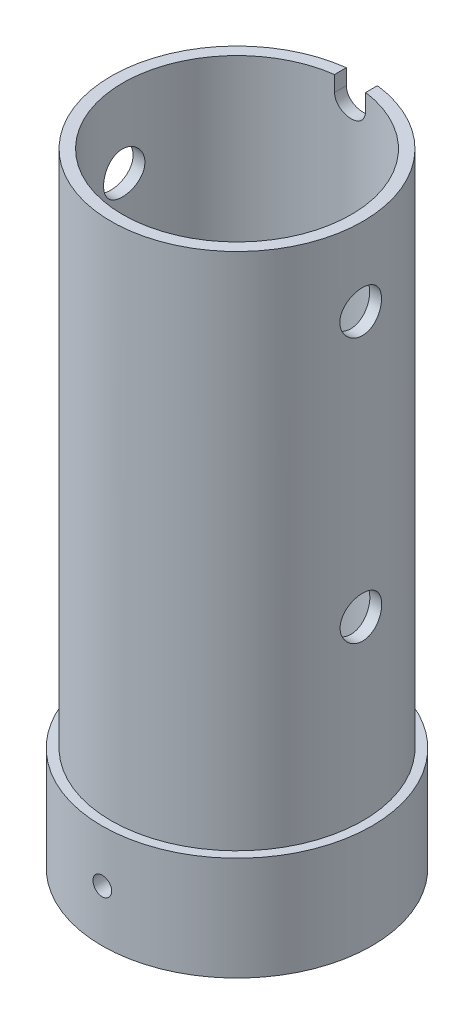
SolidWorks part; units mm, degrees
material "ABS"
ref_plane "前视基准面" through (0, 0, 0) normal (0, 0, 1) x (1, 0, 0)
ref_plane "上视基准面" through (0, 0, 0) normal (0, 1, 0) x (1, 0, 0)
ref_plane "右视基准面" through (0, 0, 0) normal (1, 0, 0) x (0, 0, -1)
sketch "草图1" plane through (0, 0, 0) normal (0, 1, 0) x (1, 0, 0)
  circle A0 centre (0, 0) radius 26
  circle A1 centre (0, 0) radius 22
  dimension "D1" = 52
  dimension "D2" = 44
extrude "凸台-拉伸1" add sketch "草图1" along normal blind 20
sketch "草图3" plane through (0, 20, 0) normal (0, 1, 0) x (1, 0, 0)
  circle A0 centre (0, 0) radius 22
  circle A1 centre (0, 0) radius 24.25
  dimension "D1" = 48.5
extrude "凸台-拉伸2" add sketch "草图3" along normal blind 100
sketch "草图4" plane through (0, 0, 0) normal (0, 0, 1) x (1, 0, 0)
  line L0 (-26, 0) -> (26, 0) construction
  line L1 (24.25, 120) -> (-24.25, 120) construction
  line L2 (-3, 120) -> (3, 120)
  line L3 (-3, 120) -> (-3, 117)
  line L5 (3, 120) -> (3, 117)
  line L6 (0, 0) -> (0, 120) construction
  circle A0 centre (0, 10) radius 1.8
  arc A1 (-3, 117) -> (3, 117) centre (0, 117) ccw
  dimension "D1" = 10
  dimension "D2" = 3.6
  dimension "D3" = 3
  dimension "D4" = 3
extrude "切除-拉伸1" cut sketch "草图4" against normal blind 100
sketch "草图5" plane through (0, 0, 0) normal (0, 0, 1) x (1, 0, 0)
  circle A0 centre (0, 10) radius 1.8
extrude "切除-拉伸2" cut sketch "草图5" along normal blind 100
sketch "草图6" plane through (0, 0, 0) normal (1, 0, 0) x (0, 0, -1)
  line L0 (0, 0) -> (-0.1028, 120) construction
  line L1 (21.7945, 120) -> (-22, 120) construction
  circle A0 centre (-0.0899, 105) radius 4
  circle A1 centre (-0.0462, 54) radius 4
  dimension "D1" = 51
  dimension "D2" = 15
  dimension "D3" = 8
  dimension "D4" = 8
extrude "切除-拉伸3" cut sketch "草图6" against normal blind 100 and the other way blind 100
